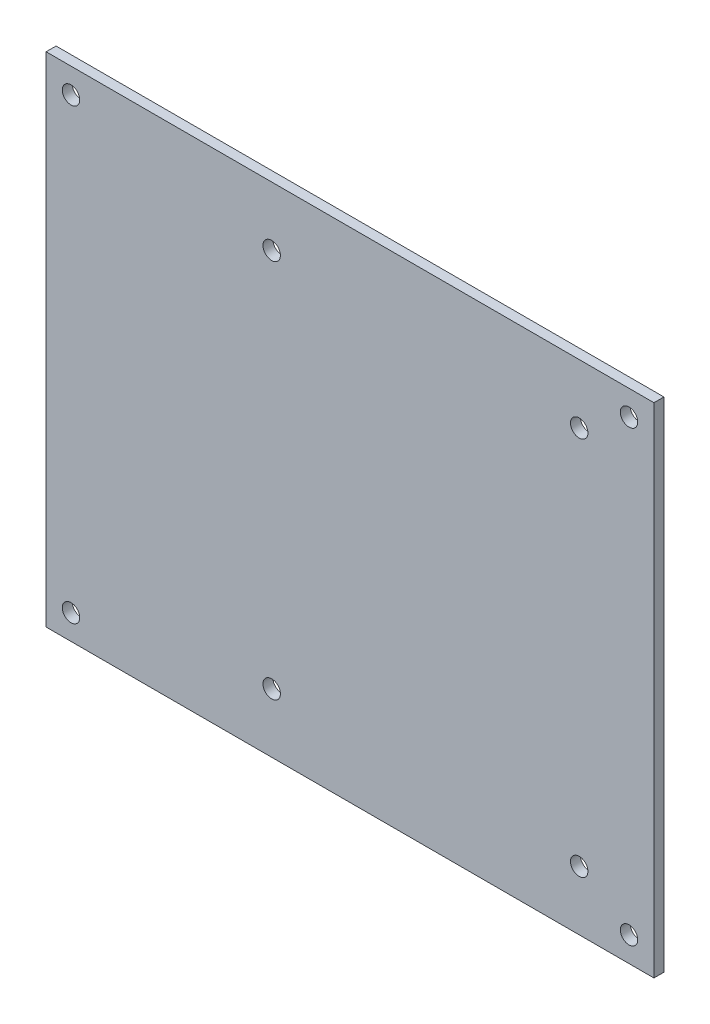
SolidWorks part; units mm, degrees
ref_plane "Front Plane" through (0, 0, 0) normal (1, 0, 0) x (0, 1, 0)
ref_plane "Top Plane" through (0, 0, 0) normal (0, 0, 1) x (0, 1, 0)
ref_plane "Right Plane" through (0, 0, 0) normal (0, 1, 0) x (-1, 0, 0)
sketch "Sketch1" plane through (0, 0, 0) normal (0, 0, 1) x (0, 1, 0)
  line L1 (50, -61) -> (-50, -61)
  line L2 (50, -61) -> (50, 61)
  line L3 (50, 61) -> (-50, 61)
  line L4 (-50, -61) -> (-50, 61)
  line L5 (50, -61) -> (-50, 61) construction
  line L6 (50, 61) -> (-50, -61) construction
  circle A0 centre (-45, 56) radius 1.75
  circle A1 centre (45, 56) radius 1.75
  circle A2 centre (-45, -56) radius 1.75
  circle A3 centre (45, -56) radius 1.75
  circle A4 centre (-38.1, -46) radius 1.75
  circle A5 centre (38.1, -46) radius 1.75
  circle A6 centre (-38.1, 15.72) radius 1.75
  circle A7 centre (38.1, 15.72) radius 1.75
  point P0 (0, 0)
  dimension "D2" = 3.5
  dimension "D8" = 3.5
  dimension "D1" = 122
  dimension "D3" = 90
  dimension "D4" = 112
  dimension "D5" = 56
  dimension "D6" = 100
  dimension "D7" = 5
  dimension "D9" = 61.72
  dimension "D10" = 76.2
  dimension "D11" = 38.1
  dimension "D12" = 15
extrude "Boss-Extrude1" add sketch "Sketch1" along normal blind 2
equation "\"D11@Sketch1\"=76.2/2"
